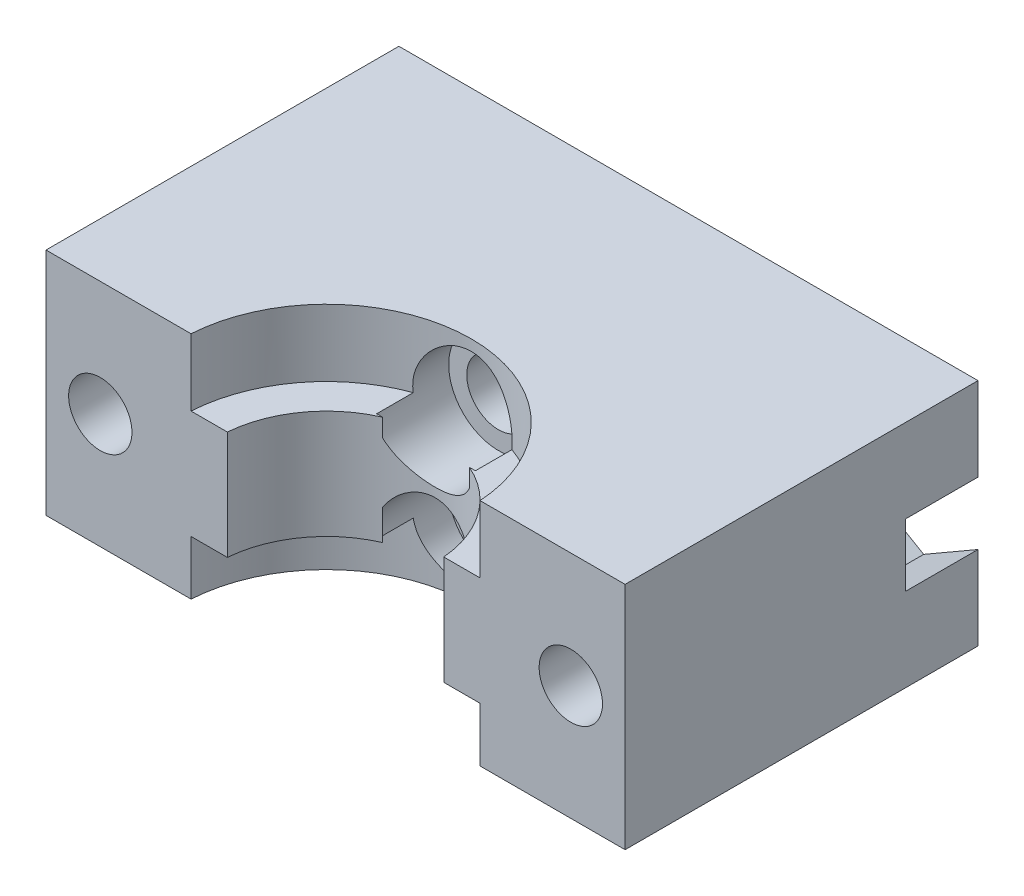
SolidWorks part; units mm, degrees
ref_plane "Front Plane" through (0, 0, 0) normal (0, 0, 1) x (1, 0, 0)
ref_plane "Top Plane" through (0, 0, 0) normal (0, 1, 0) x (1, 0, 0)
ref_plane "Right Plane" through (0, 0, 0) normal (1, 0, 0) x (0, 0, -1)
sketch "Sketch2" plane through (0, 0, 0) normal (0, 0, 1) x (1, 0, 0)
  line L0 (0, -3) -> (0, 3) construction
  line L1 (-16, 6.35) -> (16, 6.35)
  line L2 (-16, 6.35) -> (-16, -6.35)
  line L3 (-16, -6.35) -> (16, -6.35)
  line L4 (16, 6.35) -> (16, -6.35)
  line L5 (-16, 6.35) -> (16, -6.35) construction
  line L6 (-16, -6.35) -> (16, 6.35) construction
  circle A0 centre (0, 3) radius 1.75
  circle A1 centre (0, -3) radius 1.75
  point P0 (0, 0)
  dimension "D3" = 3.5
  dimension "D1" = 32
  dimension "D2" = 12.7
  dimension "D4" = 6
extrude "Boss-Extrude1" add sketch "Sketch2" along normal blind 19.5
sketch "Sketch3" plane through (0, 0, 19.5) normal (0, 0, 1) x (1, 0, 0)
  line L0 (16, 6.35) -> (-16, 6.35) construction
  line L5 (-16, -6.35) -> (16, -6.35) construction
  line L6 (-16, 6.35) -> (-10, 6.35) construction
  line L7 (-13, 6.35) -> (-13, -6.35) construction
  line L8 (10, 6.35) -> (16, 6.35) construction
  line L9 (13, 6.35) -> (13, -6.35) construction
  circle A0 centre (-13, 0) radius 1.75
  circle A1 centre (13, 0) radius 1.75
  dimension "D2" = 3.5
  dimension "D1" = 6
  dimension "D3" = 6
extrude "Cut-Extrude1" cut sketch "Sketch3" against normal through all
sketch "Sketch4" plane through (0, 0, 0) normal (0, 0, -1) x (-1, 0, 0)
  line L1 (-10, -1.7321) -> (-10, 1.7321)
  line L2 (-10, 1.7321) -> (-13, 3.4641)
  line L3 (-13, 3.4641) -> (-16, 1.7321)
  line L4 (-16, 1.7321) -> (-16, -1.7321)
  line L5 (-16, -1.7321) -> (-13, -3.4641)
  line L6 (-13, -3.4641) -> (-10, -1.7321)
  line L7 (13, -3.4641) -> (16, -1.7321)
  line L8 (16, -1.7321) -> (16, 1.7321)
  line L9 (16, 1.7321) -> (13, 3.4641)
  line L10 (13, 3.4641) -> (10, 1.7321)
  line L11 (10, 1.7321) -> (10, -1.7321)
  line L12 (10, -1.7321) -> (13, -3.4641)
  line L13 (-16, -6.35) -> (-16, 6.35) construction
  circle A0 centre (-13, 0) radius 3 construction
  circle A1 centre (13, 0) radius 3 construction
  dimension "D1" = 6
extrude "Cut-Extrude2" cut sketch "Sketch4" against normal blind 4
sketch "Sketch5" plane through (0, 6.35, 0) normal (0, 1, 0) x (1, 0, 0)
  line L0 (16, 0) -> (-16, 0) construction
  circle A0 centre (0, -20) radius 8
  dimension "D1" = 16
  dimension "D2" = 20
extrude "Cut-Extrude3" cut sketch "Sketch5" against normal blind 3.7
sketch "Sketch9" plane through (0, 2.65, 0) normal (0, 1, 0) x (1, 0, 0)
  circle A0 centre (0, -20) radius 6
  dimension "D1" = 12
extrude "Cut-Extrude5" cut sketch "Sketch9" against normal blind 6
sketch "Sketch10" plane through (0, -3.35, 0) normal (0, 1, 0) x (1, 0, 0)
  circle A0 centre (0, -20) radius 8
  dimension "D1" = 16
extrude "Cut-Extrude6" cut sketch "Sketch10" against normal through all
ref_plane "Plane1" through (0, 0, 14.5) normal (0, 0, 1) x (1, 0, 0)
sketch "Sketch6" plane through (0, 0, 14.5) normal (0, 0, 1) x (1, 0, 0)
  circle A0 centre (0, 3) radius 2.75
  circle A1 centre (0, -3) radius 2.75
  dimension "D1" = 5.5
  dimension "D2" = 5.5
extrude "Cut-Extrude4" cut sketch "Sketch6" against normal blind 4
